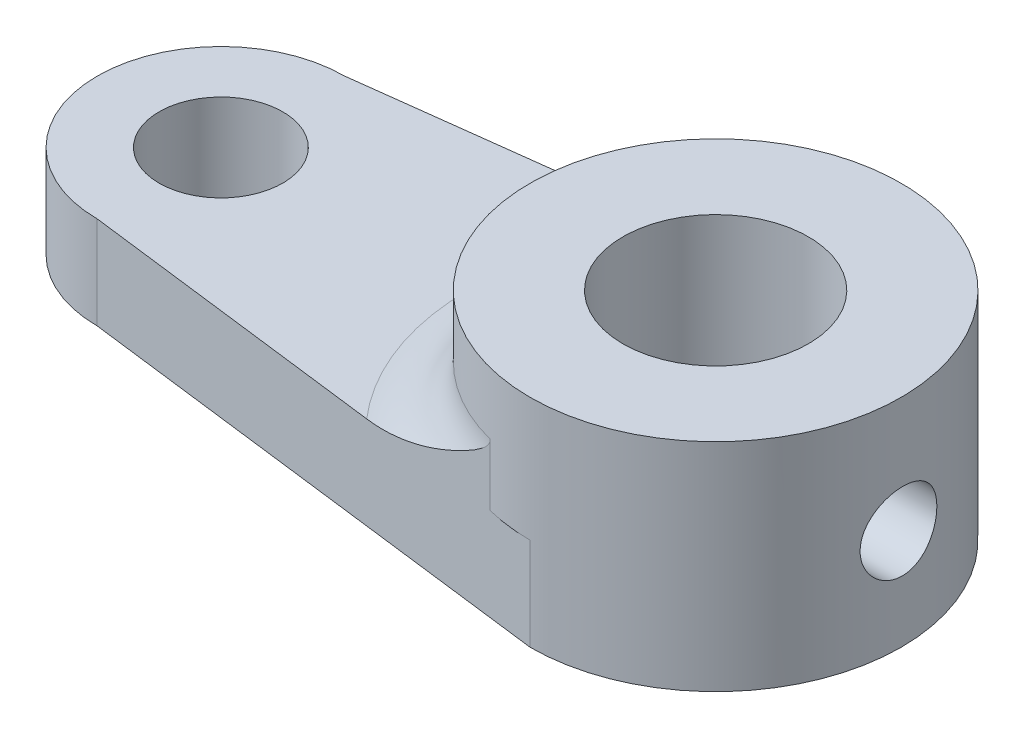
SolidWorks part; units mm, degrees
ref_plane "Front Plane" through (0, 0, 0) normal (0, 0, 1) x (1, 0, 0)
ref_plane "Top Plane" through (0, 0, 0) normal (0, 1, 0) x (1, 0, 0)
ref_plane "Right Plane" through (0, 0, 0) normal (1, 0, 0) x (0, 0, -1)
sketch "Sketch1" plane through (0, 0, 0) normal (0, 1, 0) x (1, 0, 0)
  line L1 (-51.4269, 4) -> (-35.4269, 6)
  line L2 (-51.4269, -4) -> (-35.4269, -6)
  circle A0 centre (-51.4269, 0) radius 2
  circle A1 centre (-35.4269, 0) radius 3
  circle A2 centre (-35.4269, 0) radius 6
  circle A3 centre (-51.4269, 0) radius 4
extrude "Boss-Extrude1" add sketch "Sketch1" along normal blind 3 contours A3 A0 | A3 L2 A2 L1 | L2 A2 L1 A1 region at (-44.2431, 0, 0) region at (-48.6785, 0, -2.7484) region at (-36.1443, 0, -5.7393)
sketch "Sketch2" plane through (0, 3, 0) normal (0, 1, 0) x (1, 0, 0)
  circle A0 centre (-35.4269, 0) radius 3 construction
  circle A1 centre (-35.4269, 0) radius 6 construction
  circle A2 centre (-35.4269, 0) radius 3
  circle A3 centre (-35.4269, 0) radius 6
extrude "Boss-Extrude2" add sketch "Sketch2" along normal blind 4
fillet "Fillet1" radius 2 1 edges at (-41.4269, 3, 0)
ref_plane "Plane1" through (10, 0, 0) normal (1, 0, 0) x (0, 0, -1)
hole_wizard "M3x0.5 Tapped Hole1" positions "3DSketch4" profile "Sketch4" tap size "M3x0.5" standard "ANSI Metric"
sketch3d "3DSketch4"
  point P0 (-29.4271, 3.2314, -0.0452)
sketch "Sketch4" plane through (-29.4271, 3.2314, -0.0452) normal (0, 1, 0) x (-0.0075, 0, -1)
  line L0 (0, 0) -> (0, 8.2511)
  line L1 (0, 8.2511) -> (1.25, 7.5)
  line L2 (1.25, 7.5) -> (1.25, 0)
  line L5 (1.25, 0) -> (0, 0)
  line L10 (0, 8.2511) -> (-1.25, 7.5) construction
  line L11 (0, -6.35) -> (0, 107.95) construction
  dimension "Tap Drill Dia." = 2.5
  dimension "Tap Drill Depth" = 7.5
  dimension "Drill Angle" = 118
cosmetic thread "Hole Thread1" parameters "D1"=6, "D2"=3
